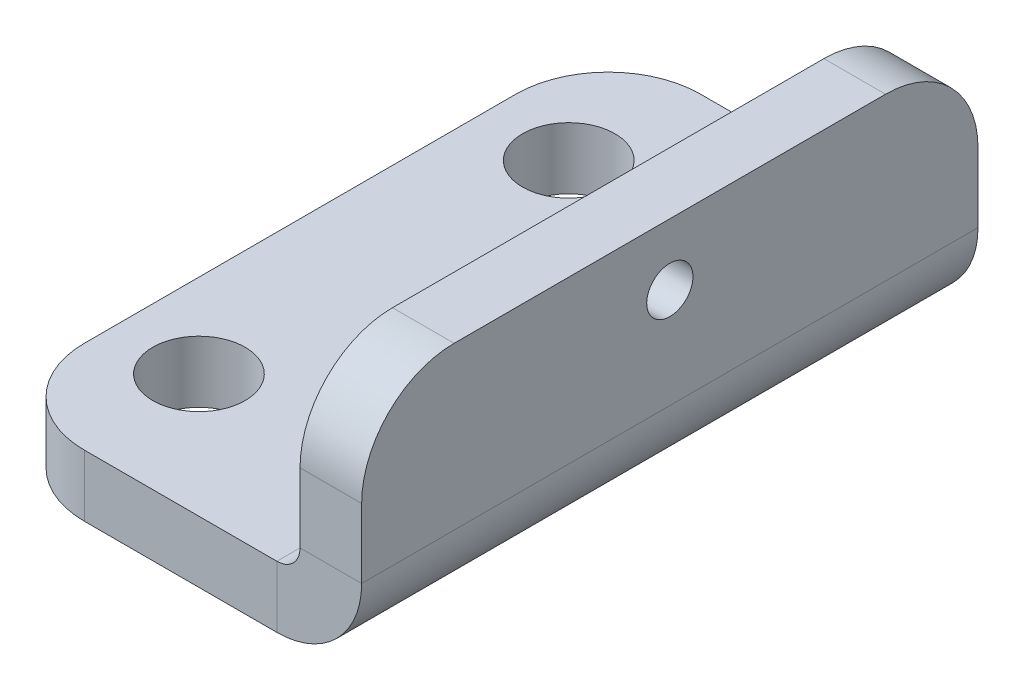
SolidWorks part; units mm, degrees
note: The reader was unsure of these and kept them because the rebuilt part matched: flange length of "Edge-Flange1".
ref_plane "Front Plane" through (0, 0, 0) normal (0, 0, 1) x (1, 0, 0)
ref_plane "Top Plane" through (0, 0, 0) normal (0, 1, 0) x (1, 0, 0)
ref_plane "Right Plane" through (0, 0, 0) normal (1, 0, 0) x (0, 0, -1)
sketch "Sketch1" plane through (0, 0, 0) normal (0, 1, 0) x (1, 0, 0)
  line L0 (0, 7) -> (0, -7)
  line L1 (3, 10) -> (12, 10)
  line L2 (3, -10) -> (12, -10)
  line L3 (12, 10) -> (12, -10)
  arc A0 (0, -7) -> (3, -10) centre (3, -7) ccw
  arc A1 (0, 7) -> (3, 10) centre (3, 7) cw
  circle A2 centre (2.72, 6) radius 1.5
  circle A3 centre (2.72, -6) radius 1.5
  point P0 (0, 6)
  point P4 (0, 0)
  point P8 (0, -6)
  point P11 (0, -10)
  point P14 (0, 10)
  dimension "D6" = 3
  dimension "D7" = 3
  dimension "D8" = 3
  dimension "D1" = 20
  dimension "D2" = 12
  dimension "D3" = 12
  dimension "D4" = 6
  dimension "D5" = 12
  dimension "D9" = 9.28
  dimension "D10" = 9.28
base flange "Base-Flange1" sketch "Sketch1" thickness 2 reverse thickness direction yes parameters "D1"=0.7366
edge flange "Edge-Flange1" sketch "Sketch8" flange angle 90 flange length 8 flange position material inside bend radius 0.75 thickness 2 relief rectangular parameters "D6"=10
sketch "Sketch8" plane through (12, 2, 0) normal (1, 0, 0) x (0, 0, -1)
  line L2 (-10, 0) -> (-10, 6)
  line L3 (-10, 6) -> (10, 6)
  line L4 (10, 6) -> (10, 0)
  line L7 (-10, 0) -> (10, 0) construction
  line L8 (-10, 0) -> (10, 0)
bend "EdgeBend1" bend radius 0.75 bend angle 90 parameters "D5"=1
sketch "Sketch9" plane through (10, 0, 0) normal (-1, 0, 0) x (0, 0, 1)
  line L0 (-10, 8) -> (10, 8) construction
  circle A0 centre (0, 6) radius 0.75
  dimension "D1" = 2
  dimension "D2" = 1.5
extrude "Cut-Extrude1" cut sketch "Sketch9" against normal blind 10 normal cut yes
fillet "Fillet1" radius 3 2 edges at (11, 8, 10) (11, 8, -10)
scale "Ölçek1" bodies to scale 103 scale about centroid uniform scaling yes scale factor 2
sketch "Bend-Lines1" [suppressed] plane through (0, 0, 0) normal (0, 1, 0) x (1, 0, 0)
sketch "Bounding-Box1" [suppressed] plane through (0, 0, 0) normal (0, 1, 0) x (1, 0, 0)
sheet metal parameters "Sheet-Metal1" thickness 2 parameters "D1"=0.7366
flat pattern "Flat-Pattern1" [suppressed]
sketch "Bend-Lines2" plane through (0, 0, 0) normal (0, 1, 0) x (1, 0, 0)
sketch3d "Bounding-Box2" [suppressed]
  line L0 (-3, 17, 0) -> (-3, -3, 0) construction
  line L1 (9, 17, 0) -> (9, -3, 0) construction
  line L2 (-3, 17, 0) -> (9, 17, 0) construction
  line L3 (-3, -3, 0) -> (9, -3, 0) construction
sheet metal parameters "Sheet-Metal2" thickness 2 parameters "D1"=0.7366
flat pattern "Flat-Pattern1"
sketch "Bend-Lines2" plane through (0, 0, 0) normal (0, -1, 0) x (-1, 0, 0)
  line L0 (-10.6244, 10) -> (-10.6244, -10) construction
  line L1 (-10.6244, 10) -> (-10.6244, -10) construction
sketch3d "Bounding-Box2" [suppressed]
  line L0 (3, 17, 0) -> (3, -3, 0) construction
  line L1 (-14.2489, 17, 0) -> (-14.2489, -3, 0) construction
  line L2 (3, 17, 0) -> (-14.2489, 17, 0) construction
  line L3 (3, -3, 0) -> (-14.2489, -3, 0) construction
bend of the flat pattern "Flatten-<EdgeBend1>1"
sheet metal parameters "Sheet-Metal3" thickness 2 parameters "D1"=0.7366
flat pattern "Flat-Pattern1"
sketch "Bend-Lines2" plane through (0, 0, 0) normal (0, -1, 0) x (-1, 0, 0)
  line L0 (-10.6244, 10) -> (-10.6244, -10) construction
  line L1 (-10.6244, 10) -> (-10.6244, -10) construction
sketch3d "Bounding-Box2" [suppressed]
  line L0 (3, 17, 0) -> (3, -3, 0) construction
  line L1 (-14.2489, 17, 0) -> (-14.2489, -3, 0) construction
  line L2 (3, 17, 0) -> (-14.2489, 17, 0) construction
  line L3 (3, -3, 0) -> (-14.2489, -3, 0) construction
bend of the flat pattern "Flatten-<EdgeBend1>1"
sheet metal parameters "Sac-Levha4" thickness 2 parameters "D1"=0.7366
flat pattern "Flat-Pattern1"
sketch "Bend-Lines2" plane through (0, 0, 0) normal (0, -1, 0) x (-1, 0, 0)
  line L0 (-10.6244, 10) -> (-10.6244, -10) construction
  line L1 (-10.6244, 10) -> (-10.6244, -10) construction
sketch3d "Bounding-Box2" [suppressed]
  line L0 (3, 17, 0) -> (3, -3, 0) construction
  line L1 (-14.2489, 17, 0) -> (-14.2489, -3, 0) construction
  line L2 (3, 17, 0) -> (-14.2489, 17, 0) construction
  line L3 (3, -3, 0) -> (-14.2489, -3, 0) construction
bend of the flat pattern "Flatten-<EdgeBend1>1"
